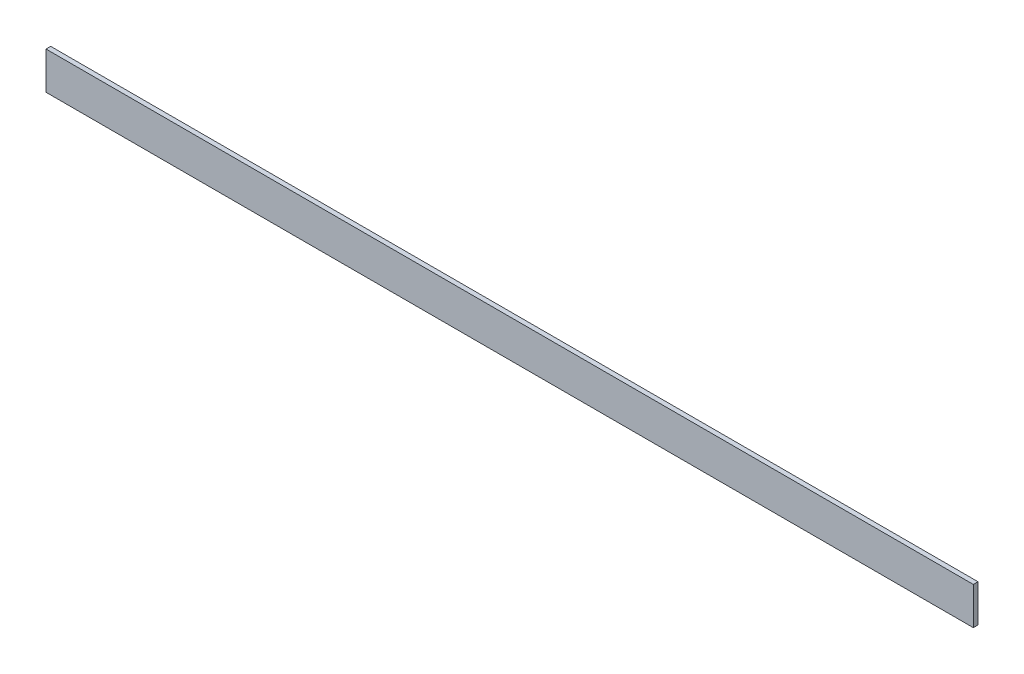
SolidWorks part; units mm, degrees
ref_plane "Front" through (0, 0, 0) normal (0, 0, 1) x (1, 0, 0)
ref_plane "Top" through (0, 0, 0) normal (0, 1, 0) x (1, 0, 0)
ref_plane "Right" through (0, 0, 0) normal (1, 0, 0) x (0, 0, -1)
sketch "Sketch1" plane through (0, 0, 0) normal (1, 0, 0) x (0, 0, -1)
  line L1 (0, 0) -> (3.175, 0)
  line L2 (0, 0) -> (0, 25.4)
  line L3 (0, 25.4) -> (3.175, 25.4)
  line L4 (3.175, 0) -> (3.175, 25.4)
  line L5 (0, 0) -> (3.175, 25.4) construction
  line L6 (0, 25.4) -> (3.175, 0) construction
  point P4 (1.5875, 12.7)
  dimension "D1" = 25.4
  dimension "D2" = 3.175
extrude "Boss-Extrude1" add sketch "Sketch1" along normal blind 628.65
